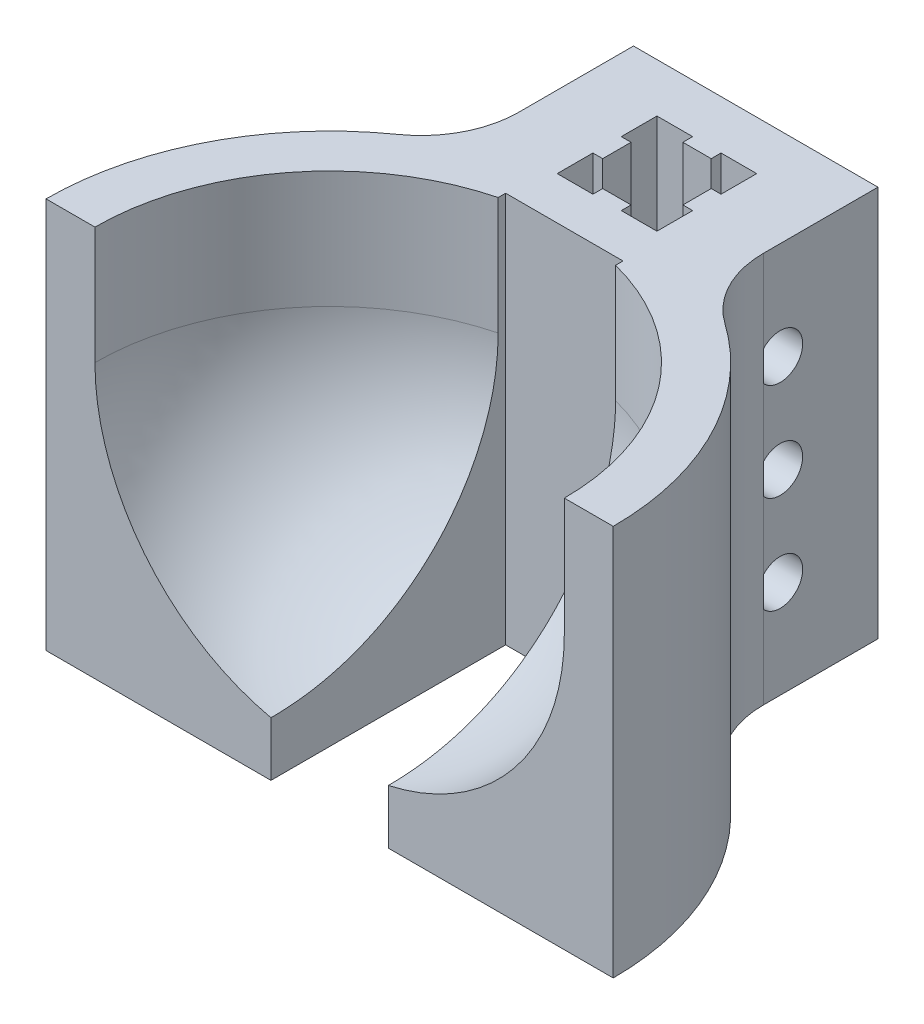
SolidWorks part; units mm, degrees
ref_plane "Front Plane" through (0, 0, 0) normal (0, 0, 1) x (1, 0, 0)
ref_plane "Top Plane" through (0, 0, 0) normal (0, 1, 0) x (1, 0, 0)
ref_plane "Right Plane" through (0, 0, 0) normal (1, 0, 0) x (0, 0, -1)
ref_axis "Axe1" through (0, -1.5691, 0) along (0, 1, 0)
sketch "Esquisse2" plane through (0, 0, 0) normal (-1, 0, 0) x (0, 0, 1)
  line L0 (-24, 40) -> (-29, 40)
  line L1 (-29, 40) -> (-29, 0)
  line L2 (-29, 0) -> (0, 0)
  line L3 (-1, 5) -> (0, 5)
  line L4 (-24, 40) -> (-24, 28)
  line L6 (0, 5) -> (0, 0)
  line L7 (0, -1.5691) -> (0, 32.9511) construction
  arc A0 (-24, 28) -> (-1, 5) centre (-1, 28) ccw
  dimension "D3" = 23
  dimension "D1" = 5
  dimension "D2" = 1
  dimension "D4" = 40
  dimension "D5" = 5
revolve "Révolution1" add sketch "Esquisse2" angle 180 mid plane about axis through (0, -1.5691, 0) along (0, 1, 0)
sketch "Esquisse3" plane through (0, 40, 0) normal (0, -1, 0) x (1, 0, 0)
  line L1 (-6, 0) -> (6, 0)
  line L2 (-6, 0) -> (-6, -24)
  line L3 (-6, -24) -> (6, -24)
  line L4 (6, 0) -> (6, -24)
  line L8 (-6, -28.3725) -> (6, -28.3725)
  line L9 (-6, -28.3725) -> (-6, -29)
  line L10 (-6, -29) -> (6, -29)
  line L11 (6, -28.3725) -> (6, -29)
  arc A0 (-29, 0) -> (29, 0) centre (0, 0) ccw construction
  arc A1 (-24, 0) -> (24, 0) centre (0, 0) ccw construction
  point P6 (0, 0)
  dimension "D1" = 12
extrude "Ball Hole" cut sketch "Esquisse3" along normal through all
sketch "Esquisse4" plane through (0, 0, 0) normal (0, -1, 0) x (-1, 0, 0)
  line L0 (-6, 28.3725) -> (6, 28.3725) construction
  line L1 (1.45, 28.3725) -> (5.1, 28.3725)
  line L2 (1.45, 28.3725) -> (1.45, 29.3725)
  line L3 (1.45, 29.3725) -> (-1.45, 29.3725)
  line L4 (-1.45, 28.3725) -> (-1.45, 29.3725)
  line L5 (5.1, 28.3725) -> (5.1, 32.0225)
  line L6 (5.1, 32.0225) -> (4.1, 32.0225)
  line L7 (4.1, 32.0225) -> (4.1, 34.9225)
  line L8 (4.1, 34.9225) -> (5.1, 34.9225)
  line L9 (5.1, 34.9225) -> (5.1, 38.5725)
  line L10 (5.1, 38.5725) -> (1.45, 38.5725)
  line L11 (1.45, 38.5725) -> (1.45, 37.5725)
  line L12 (1.45, 37.5725) -> (-1.45, 37.5725)
  line L13 (-1.45, 37.5725) -> (-1.45, 38.5725)
  line L14 (-1.45, 38.5725) -> (-5.1, 38.5725)
  line L15 (-5.1, 38.5725) -> (-5.1, 34.9225)
  line L16 (-5.1, 34.9225) -> (-4.1, 34.9225)
  line L17 (-4.1, 34.9225) -> (-4.1, 32.0225)
  line L18 (-4.1, 32.0225) -> (-5.1, 32.0225)
  line L19 (-5.1, 32.0225) -> (-5.1, 28.3725)
  line L20 (-5.1, 28.3725) -> (-1.45, 28.3725)
  line L21 (5.1, 32.0225) -> (12.5, 32.0225) construction
  line L22 (12.5, 24) -> (-12.5, 24)
  line L23 (12.5, 24) -> (12.5, 43.5725)
  line L24 (12.5, 43.5725) -> (-12.5, 43.5725)
  line L25 (-12.5, 24) -> (-12.5, 43.5725)
  line L26 (-5.1, 32.0225) -> (-12.5, 32.0225) construction
  line L27 (6, 24) -> (-6, 24) construction
  point P7 (0, 28.3725)
  point P40 (0, 29.3725)
  dimension "D1" = 2.9
  dimension "D2" = 1
  dimension "D3" = 10.2
  dimension "D4" = 10.2
  dimension "D5" = 5
  dimension "D6" = 25
extrude "Fixing Support" add sketch "Esquisse4" against normal through all
fillet "Congé1" radius 10 2 edges at (-12.5, 20, -26.1677) (12.5, 20, -26.1677)
sketch "Esquisse5" plane through (0, 0, -43.5725) normal (0, 0, -1) x (-1, 0, 0)
  line L3 (0, -1.5691) -> (0, 32.9511) construction
  line L4 (6, 0) -> (-6, 0) construction
  line L5 (6, 40) -> (-6, 40) construction
  circle A0 centre (0, 8) radius 1.6
  circle A1 centre (0, 32) radius 1.6
  dimension "D1" = 3.2
  dimension "D2" = 8
  dimension "D3" = 8
extrude "Fixing Hole" cut sketch "Esquisse5" against normal up to next
sketch "Esquisse7" plane through (0, 0, -43.5725) normal (0, 0, -1) x (-1, 0, 0)
  circle A0 centre (0, 32) radius 4.25
  circle A1 centre (0, 8) radius 4.25
  dimension "D1" = 8.5
extrude "Fixing Screw Hole" cut sketch "Esquisse7" against normal blind 2
sketch "Esquisse6" plane through (-12.5, 0, 0) normal (-1, 0, 0) x (0, 0, 1)
  line L2 (-43.5725, 40) -> (-43.5725, 0) construction
  line L3 (-31.8551, 40) -> (-43.5725, 40) construction
  circle A0 centre (-33.5725, 30) radius 2.3
  dimension "D1" = 4.6
  dimension "D2" = 10
  dimension "D3" = 10
extrude "Ressort Hole" cut sketch "Esquisse6" against normal blind 7
pattern_linear "Répétition linéaire1" count 3 spacing 10 along (0, -1, 0) of "Ressort Hole"
mirror "Symétrie1" about plane through (0, 0, 0) normal (1, 0, 0) of "Répétition linéaire1"
